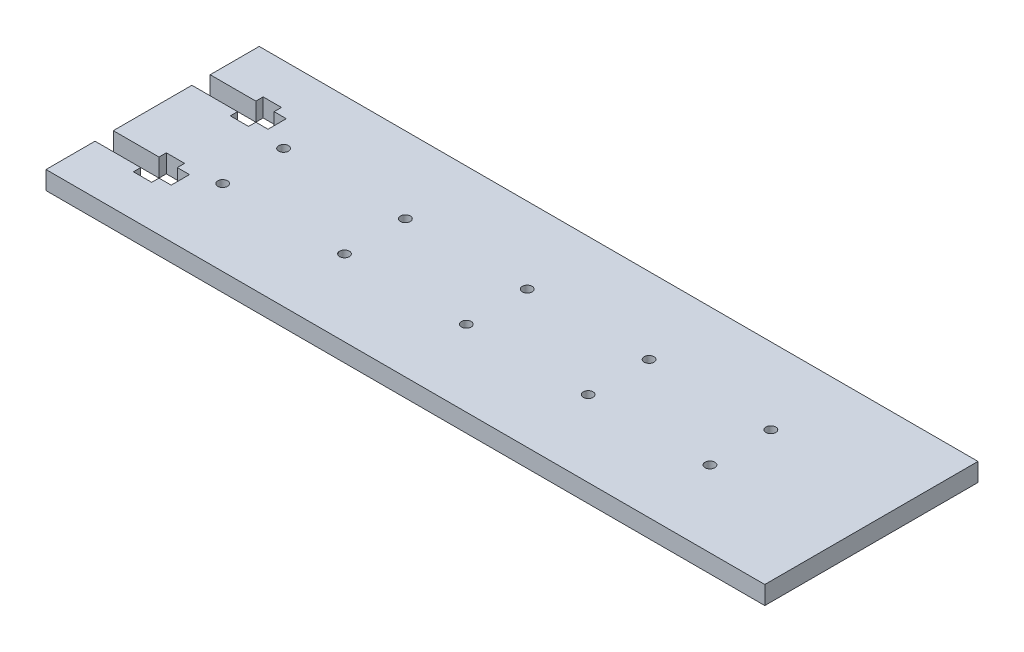
SolidWorks part; units mm, degrees
ref_plane "Front Plane" through (0, 0, 0) normal (0, 0, 1) x (1, 0, 0)
ref_plane "Top Plane" through (0, 0, 0) normal (0, 1, 0) x (1, 0, 0)
ref_plane "Right Plane" through (0, 0, 0) normal (1, 0, 0) x (0, 0, -1)
sketch "Sketch1" plane through (0, 0, 0) normal (0, 1, 0) x (1, 0, 0)
  line L1 (-118, -35) -> (118, -35)
  line L2 (-118, -35) -> (-118, 35)
  line L3 (-118, 35) -> (118, 35)
  line L4 (118, -35) -> (118, 35)
  line L5 (-118, -35) -> (118, 35) construction
  line L6 (-118, 35) -> (118, -35) construction
  circle A0 centre (75, -10) radius 1.6 construction
  circle A1 centre (75, 10) radius 1.6 construction
  circle A2 centre (35, -10) radius 1.6 construction
  circle A3 centre (35, 10) radius 1.6 construction
  circle A4 centre (-5, -10) radius 1.6 construction
  circle A5 centre (-5, 10) radius 1.6 construction
  circle A6 centre (-45, -10) radius 1.6 construction
  circle A7 centre (-45, 10) radius 1.6 construction
  circle A8 centre (-85, -10) radius 1.6 construction
  circle A9 centre (-85, 10) radius 1.6 construction
  circle A10 centre (75, -10) radius 1.6
  circle A11 centre (75, 10) radius 1.6
  circle A12 centre (35, -10) radius 1.6
  circle A13 centre (35, 10) radius 1.6
  circle A14 centre (-5, -10) radius 1.6
  circle A15 centre (-5, 10) radius 1.6
  circle A16 centre (-45, -10) radius 1.6
  circle A17 centre (-45, 10) radius 1.6
  circle A18 centre (-85, -10) radius 1.6
  circle A19 centre (-85, 10) radius 1.6
  point P0 (0, 0)
  dimension "D1" = 236
  dimension "D2" = 70
extrude "Boss-Extrude1" add sketch "Sketch1" along normal blind 6
sketch "Sketch3" plane through (0, 6, 0) normal (0, 1, 0) x (1, 0, 0)
  line L0 (-118, 0) -> (-93, 0) construction
  line L1 (-118, 35) -> (-118, -35) construction
  line L2 (-118, 15.9) -> (-93, 15.9) construction
  line L7 (-118, 12.9) -> (-103, 12.9)
  line L8 (-118, 18.9) -> (-103, 18.9)
  line L9 (-118, 12.9) -> (-118, 18.9)
  line L10 (-93, 12.9) -> (-93, 18.9)
  line L18 (-103, 10.5) -> (-97, 10.5)
  line L19 (-103, 10.5) -> (-103, 12.9)
  line L20 (-103, 21.3) -> (-97, 21.3)
  line L21 (-97, 10.5) -> (-97, 12.9)
  line L22 (-103, 10.5) -> (-97, 21.3) construction
  line L23 (-103, 21.3) -> (-97, 10.5) construction
  line L29 (-97, 18.9) -> (-97, 21.3)
  line L30 (-97, 18.9) -> (-93, 18.9)
  line L31 (-118, 18.9) -> (-93, 18.9) construction
  line L32 (-97, 12.9) -> (-93, 12.9)
  line L33 (-118, 12.9) -> (-93, 12.9) construction
  line L34 (-103, 18.9) -> (-103, 21.3)
  line L35 (-103, -21.3) -> (-97, -10.5) construction
  line L36 (-103, -10.5) -> (-97, -21.3) construction
  line L37 (-118, -15.9) -> (-93, -15.9) construction
  line L38 (-103, -18.9) -> (-103, -21.3)
  line L39 (-97, -12.9) -> (-93, -12.9)
  line L40 (-97, -18.9) -> (-93, -18.9)
  line L41 (-97, -18.9) -> (-97, -21.3)
  line L42 (-97, -10.5) -> (-97, -12.9)
  line L43 (-103, -21.3) -> (-97, -21.3)
  line L44 (-103, -10.5) -> (-103, -12.9)
  line L45 (-103, -10.5) -> (-97, -10.5)
  line L46 (-93, -12.9) -> (-93, -18.9)
  line L47 (-118, -12.9) -> (-118, -18.9)
  line L48 (-118, -18.9) -> (-103, -18.9)
  line L49 (-118, -12.9) -> (-103, -12.9)
  point P11 (-100, 15.9)
  point P47 (-100, -15.9)
  dimension "D3" = 15
  dimension "D4" = 15.9
  dimension "D7" = 25
  dimension "D1" = 10.8
  dimension "D2" = 6
  dimension "D5" = 3
  dimension "D6" = 3
extrude "Cut-Extrude2" cut sketch "Sketch3" against normal through all
